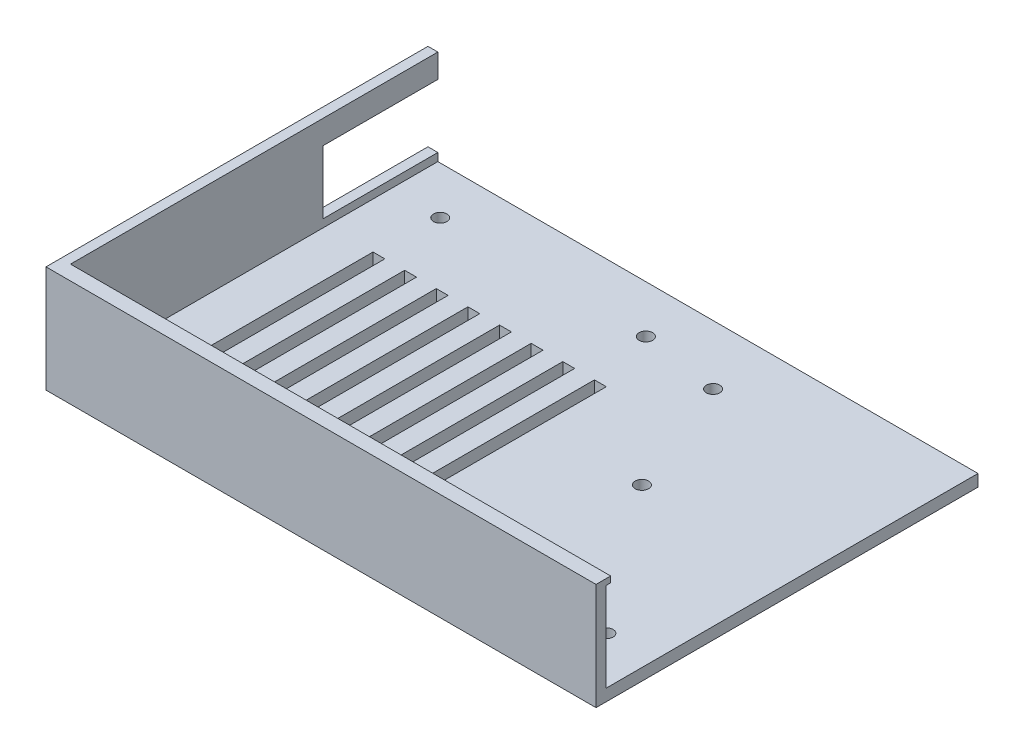
SolidWorks part; units mm, degrees
ref_plane "Front Plane" through (0, 0, 0) normal (0, 0, 1) x (1, 0, 0)
ref_plane "Top Plane" through (0, 0, 0) normal (0, 1, 0) x (1, 0, 0)
ref_plane "Right Plane" through (0, 0, 0) normal (1, 0, 0) x (0, 0, -1)
sketch "Sketch1" plane through (0, 0, 0) normal (0, 1, 0) x (1, 0, 0)
  line L1 (-139.1, -96.6) -> (139.1, -96.6)
  line L2 (-139.1, -96.6) -> (-139.1, 96.6)
  line L3 (-139.1, 96.6) -> (139.1, 96.6)
  line L4 (139.1, -96.6) -> (139.1, 96.6)
  line L5 (-139.1, -96.6) -> (139.1, 96.6) construction
  line L6 (-139.1, 96.6) -> (139.1, -96.6) construction
  dimension "D1" = 278.2
  dimension "D2" = 193.2
extrude "Shell Block" add sketch "Sketch1" along normal blind 27
ref_plane "Shell Front" through (0, 27, 0) normal (0, 1, 0) x (1, 0, 0)
sketch "Sketch2" plane through (0, 27, 0) normal (0, 1, 0) x (1, 0, 0)
  line L1 (-136.6, -92.9) -> (136.6, -92.9)
  line L2 (-136.6, -92.9) -> (-136.6, 92.9)
  line L3 (-136.6, 92.9) -> (136.6, 92.9)
  line L4 (136.6, -92.9) -> (136.6, 92.9)
  line L5 (-136.6, -92.9) -> (136.6, 92.9) construction
  line L6 (-136.6, 92.9) -> (136.6, -92.9) construction
  dimension "D1" = 273.2
  dimension "D2" = 185.8
extrude "Front Opening" cut sketch "Sketch2" against normal blind 1.5
ref_plane "Under Lip" through (0, 25.5, 0) normal (0, 1, 0) x (1, 0, 0)
sketch "Sketch3" plane through (0, 25.5, 0) normal (0, 1, 0) x (1, 0, 0)
  line L1 (-136.6, -94.1) -> (136.6, -94.1)
  line L2 (-136.6, -94.1) -> (-136.6, 94.1)
  line L3 (-136.6, 94.1) -> (136.6, 94.1)
  line L4 (136.6, -94.1) -> (136.6, 94.1)
  line L5 (-136.6, -94.1) -> (136.6, 94.1) construction
  line L6 (-136.6, 94.1) -> (136.6, -94.1) construction
  dimension "D1" = 273.2
  dimension "D2" = 188.2
extrude "Display Pocket" cut sketch "Sketch3" against normal blind 22.5
ref_plane "Back Inner" through (0, 3, 0) normal (0, 1, 0) x (1, 0, 0)
sketch "Sketch4" plane through (0, 3, 0) normal (0, 1, 0) x (1, 0, 0)
  line L1 (-69, 28) -> (-66, 28)
  line L2 (-69, 28) -> (-69, 84)
  line L3 (-69, 84) -> (-66, 84)
  line L4 (-66, 28) -> (-66, 84)
  line L6 (-69, -84) -> (-66, -84)
  line L7 (-69, -84) -> (-69, -28)
  line L8 (-69, -28) -> (-66, -28)
  line L9 (-66, -84) -> (-66, -28)
  line L11 (-77, 28) -> (-74, 28)
  line L12 (-77, 28) -> (-77, 84)
  line L13 (-77, 84) -> (-74, 84)
  line L14 (-74, 28) -> (-74, 84)
  line L16 (-77, -84) -> (-74, -84)
  line L17 (-77, -84) -> (-77, -28)
  line L18 (-77, -28) -> (-74, -28)
  line L19 (-74, -84) -> (-74, -28)
  line L21 (-85, 28) -> (-82, 28)
  line L22 (-85, 28) -> (-85, 84)
  line L23 (-85, 84) -> (-82, 84)
  line L24 (-82, 28) -> (-82, 84)
  line L26 (-85, -84) -> (-82, -84)
  line L27 (-85, -84) -> (-85, -28)
  line L28 (-85, -28) -> (-82, -28)
  line L29 (-82, -84) -> (-82, -28)
  line L31 (-93, 28) -> (-90, 28)
  line L32 (-93, 28) -> (-93, 84)
  line L33 (-93, 84) -> (-90, 84)
  line L34 (-90, 28) -> (-90, 84)
  line L36 (-93, -84) -> (-90, -84)
  line L37 (-93, -84) -> (-93, -28)
  line L38 (-93, -28) -> (-90, -28)
  line L39 (-90, -84) -> (-90, -28)
  line L41 (-101, 28) -> (-98, 28)
  line L42 (-101, 28) -> (-101, 84)
  line L43 (-101, 84) -> (-98, 84)
  line L44 (-98, 28) -> (-98, 84)
  line L46 (-101, -84) -> (-98, -84)
  line L47 (-101, -84) -> (-101, -28)
  line L48 (-101, -28) -> (-98, -28)
  line L49 (-98, -84) -> (-98, -28)
  line L51 (-109, 28) -> (-106, 28)
  line L52 (-109, 28) -> (-109, 84)
  line L53 (-109, 84) -> (-106, 84)
  line L54 (-106, 28) -> (-106, 84)
  line L56 (-109, -84) -> (-106, -84)
  line L57 (-109, -84) -> (-109, -28)
  line L58 (-109, -28) -> (-106, -28)
  line L59 (-106, -84) -> (-106, -28)
  line L61 (-117, 28) -> (-114, 28)
  line L62 (-117, 28) -> (-117, 84)
  line L63 (-117, 84) -> (-114, 84)
  line L64 (-114, 28) -> (-114, 84)
  line L66 (-117, -84) -> (-114, -84)
  line L67 (-117, -84) -> (-117, -28)
  line L68 (-117, -28) -> (-114, -28)
  line L69 (-114, -84) -> (-114, -28)
  line L71 (-125, 28) -> (-122, 28)
  line L72 (-125, 28) -> (-125, 84)
  line L73 (-125, 84) -> (-122, 84)
  line L74 (-122, 28) -> (-122, 84)
  line L76 (-125, -84) -> (-122, -84)
  line L77 (-125, -84) -> (-125, -28)
  line L78 (-125, -28) -> (-122, -28)
  line L79 (-122, -84) -> (-122, -28)
extrude "Vent Slots" cut sketch "Sketch4" against normal blind 4
sketch "Sketch5" plane through (0, 0, 0) normal (1, 0, 0) x (0, 0, -1)
  line L1 (-29, 5) -> (29, 5)
  line L2 (-29, 5) -> (-29, 21)
  line L3 (-29, 21) -> (29, 21)
  line L4 (29, 5) -> (29, 21)
extrude "Cable Exit (-X short side)" cut sketch "Sketch5" against normal blind 140.1
sketch "Sketch6" plane through (0, 3, 0) normal (0, 1, 0) x (1, 0, 0)
  circle A0 centre (-40, -45) radius 1.7
  circle A1 centre (-40, 45) radius 1.7
  circle A2 centre (40, -45) radius 1.7
  circle A3 centre (40, 45) radius 1.7
  circle A4 centre (-52, -15) radius 1.7
  circle A5 centre (-52, 15) radius 1.7
  circle A6 centre (52, -15) radius 1.7
  circle A7 centre (52, 15) radius 1.7
  circle A8 centre (-12, -82) radius 1.7
  circle A9 centre (-12, 82) radius 1.7
  circle A10 centre (12, -82) radius 1.7
  circle A11 centre (12, 82) radius 1.7
  circle A12 centre (-124, -12) radius 1.7
  circle A13 centre (-124, 12) radius 1.7
  circle A14 centre (124, -12) radius 1.7
  circle A15 centre (124, 12) radius 1.7
  circle A16 centre (-72, 12) radius 1.7
  circle A17 centre (-72, -12) radius 1.7
extrude "Bolt Holes" cut sketch "Sketch6" against normal blind 4
sketch "Sketch7" plane through (0, 0, 0) normal (0, 1, 0) x (1, 0, 0)
  line L1 (200, -200) -> (0, -200)
  line L2 (200, -200) -> (200, 200)
  line L3 (200, 200) -> (0, 200)
  line L4 (0, -200) -> (0, 200)
extrude "Keep one half (X)" cut sketch "Sketch7" against normal through all and the other way through all
sketch "Sketch8" plane through (0, 0, 0) normal (0, 1, 0) x (1, 0, 0)
  line L1 (-200, 0) -> (200, 0)
  line L2 (-200, 0) -> (-200, 200)
  line L3 (-200, 200) -> (200, 200)
  line L4 (200, 0) -> (200, 200)
extrude "Keep one quarter (Z)" cut sketch "Sketch8" against normal through all and the other way through all
equation "\"DispL\"= 272.0"
equation "\"DispW\"= 187.0"
equation "\"DispT\"= 20.0"
equation "\"Clr\"= 0.6"
equation "\"Wall\"= 2.5"
equation "\"BackT\"= 3.0"
equation "\"CableRoom\"= 4.0"
equation "\"LipW\"= 1.2"
equation "\"LipT\"= 1.5"
equation "\"CableW\"= 58.0"
equation "\"CableH\"= 16.0"
equation "\"BoltD\"= 3.4"
equation "\"ShellL\"= \"DispL\" + 2 * \"Clr\" + 2 * \"Wall\""
equation "\"ShellW\"= \"DispW\" + 2 * \"Clr\" + 2 * \"Wall\""
equation "\"ShellH\"= \"BackT\" + \"DispT\" + \"CableRoom\""
equation "\"D1@Sketch1\" = \"ShellL\""
equation "\"D2@Sketch1\" = \"ShellW\""
equation "\"D1@Shell Block\" = \"ShellH\""
equation "\"D1@Shell Front\" = \"ShellH\""
equation "\"D1@Sketch2\" = \"DispL\" + 2 * \"Clr\""
equation "\"D2@Sketch2\" = \"DispW\" + 2 * \"Clr\" - 2 * \"LipW\""
equation "\"D1@Front Opening\" = \"LipT\""
equation "\"D1@Under Lip\" = \"ShellH\" - \"LipT\""
equation "\"D1@Sketch3\" = \"DispL\" + 2 * \"Clr\""
equation "\"D2@Sketch3\" = \"DispW\" + 2 * \"Clr\""
equation "\"D1@Display Pocket\" = \"ShellH\" - \"LipT\" - \"BackT\""
equation "\"D1@Back Inner\" = \"BackT\""
